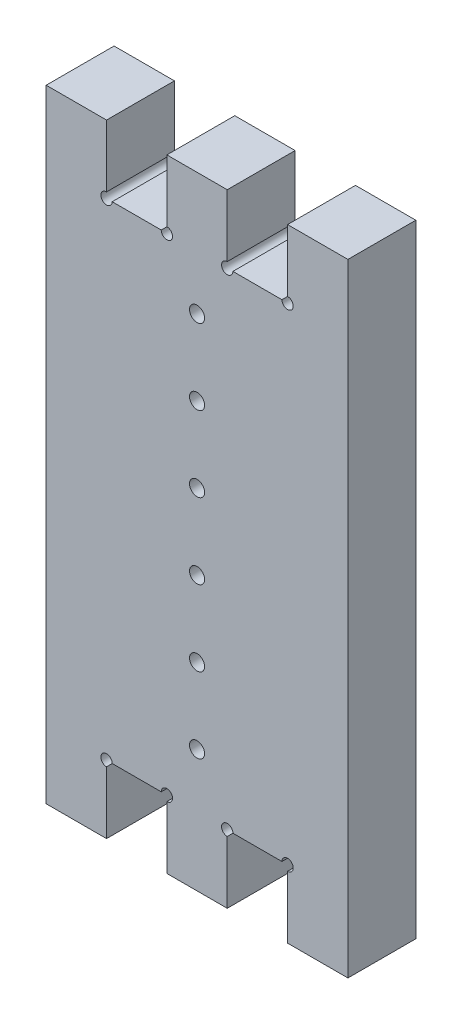
SolidWorks part; units mm, degrees
ref_plane "Front Plane" through (0, 0, 0) normal (0, 0, 1) x (1, 0, 0)
ref_plane "Top Plane" through (0, 0, 0) normal (0, 1, 0) x (1, 0, 0)
ref_plane "Right Plane" through (0, 0, 0) normal (1, 0, 0) x (0, 0, -1)
sketch "Sketch1" plane through (0, 0, 0) normal (0, 0, 1) x (1, 0, 0)
  line L0 (-1739.7044, 0) -> (85245.5138, 0) construction
  line L1 (0, -1739.7044) -> (0, 85245.5138) construction
  line L2 (-24, 64.5) -> (-8, 64.5)
  line L5 (-8, 82.5) -> (8, 82.5)
  line L7 (-24, 82.5) -> (-24, 64.5)
  line L8 (-8, 82.5) -> (-8, 64.5)
  line L9 (8, 82.5) -> (8, 64.5)
  line L10 (24, 82.5) -> (24, 64.5)
  line L22 (8, -64.5) -> (24, -64.5)
  line L23 (-24, 82.5) -> (-40, 82.5)
  line L24 (-40, 82.5) -> (-40, -82.5)
  line L25 (24, 82.5) -> (40, 82.5)
  line L26 (40, 82.5) -> (40, -82.5)
  line L27 (8, 64.5) -> (24, 64.5)
  line L28 (24, -82.5) -> (40, -82.5)
  line L29 (-24, -82.5) -> (-40, -82.5)
  line L30 (24, -82.5) -> (24, -64.5)
  line L31 (8, -82.5) -> (8, -64.5)
  line L32 (-8, -82.5) -> (-8, -64.5)
  line L33 (-24, -82.5) -> (-24, -64.5)
  line L34 (-8, -82.5) -> (8, -82.5)
  line L35 (-24, -64.5) -> (-8, -64.5)
  line L36 (-1739.7044, -40) -> (85245.5138, -40) construction
  line L37 (-1739.7044, 40) -> (85245.5138, 40) construction
  circle A0 centre (0, 50) radius 2
  circle A1 centre (0, 30) radius 2
  circle A2 centre (0, -30) radius 2
  circle A3 centre (0, -50) radius 2
  circle A4 centre (0, 10) radius 2
  circle A5 centre (0, -10) radius 2
  point P17 (-40, 0)
  point P23 (0, 82.5)
  dimension "D9" = 4
  dimension "D1" = 165
  dimension "D2" = 80
  dimension "D3" = 18
  dimension "D4" = 40
  dimension "D6" = 40
  dimension "D7" = 16
  dimension "D10" = 10
  dimension "D12" = 10
  dimension "D8" = 40
  dimension "D5" = 4
  dimension "D11" = 2
extrude "Boss-Extrude1" add sketch "Sketch1" along normal blind 18
sketch "Sketch2" plane through (0, 0, 18) normal (0, 0, 1) x (1, 0, 0)
  line L0 (-1000, 0) -> (49000, 0) construction
  circle A0 centre (-24, 64.5) radius 1.5
  circle A1 centre (-8, 64.5) radius 1.5
  circle A2 centre (8, 64.5) radius 1.5
  circle A3 centre (24, 64.5) radius 1.5
  circle A4 centre (24, -64.5) radius 1.5
  circle A5 centre (8, -64.5) radius 1.5
  circle A6 centre (-8, -64.5) radius 1.5
  circle A7 centre (-24, -64.5) radius 1.5
  dimension "D1" = 3
  dimension "D3" = 16
  dimension "D2" = 4
extrude "Cut-Extrude1" cut sketch "Sketch2" against normal through all
